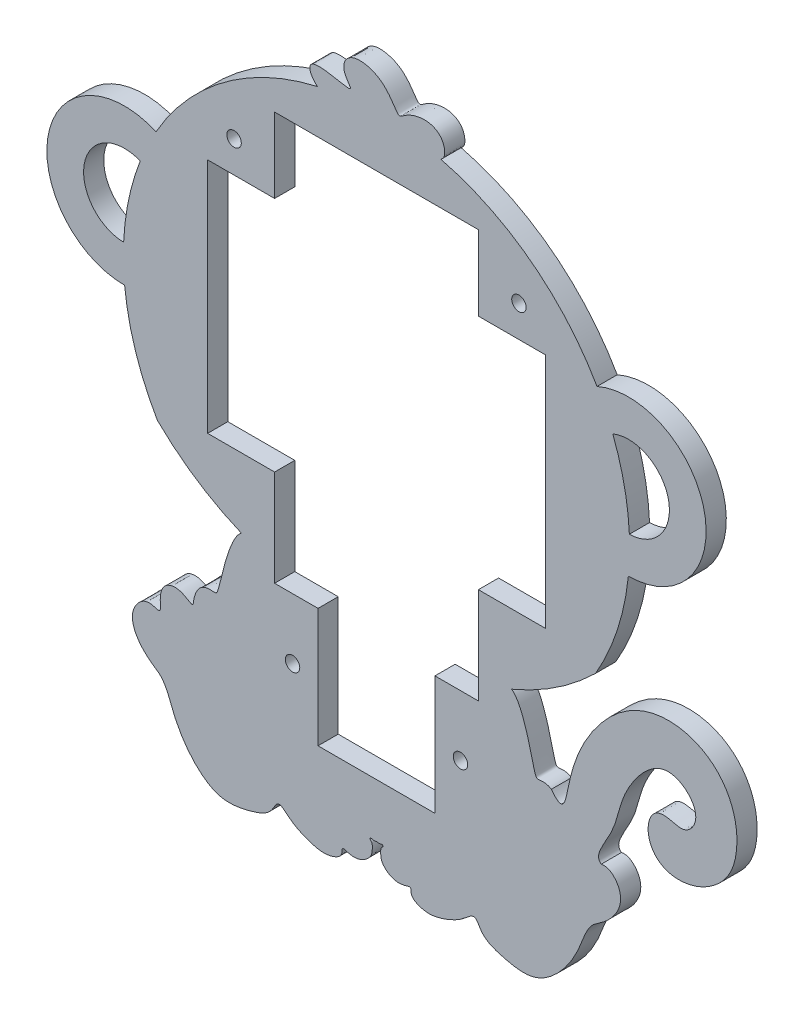
SolidWorks part; units mm, degrees
ref_plane "Front Plane" through (0, 0, 0) normal (0, 0, 1) x (1, 0, 0)
ref_plane "Top Plane" through (0, 0, 0) normal (0, 1, 0) x (1, 0, 0)
ref_plane "Right Plane" through (0, 0, 0) normal (1, 0, 0) x (0, 0, -1)
sketch "Model" plane through (0, 0, 0) normal (0, 0, 1) x (1, 0, 0)
  line L0 (-354.7776, 349.4226) -> (-354.7776, 392.0292) construction
  line L1 (-368.5276, 390.0292) -> (-368.5276, 362.0292)
  line L2 (-368.5276, 390.0292) -> (-341.0276, 390.0292)
  line L21 (-354.7776, 390.0292) -> (-354.7776, 362.0292)
  line L26 (-368.5276, 362.0292) -> (-341.0276, 362.0292)
  line L27 (-341.0276, 390.0292) -> (-341.0276, 362.0292)
  line L28 (-354.7776, 390.0292) -> (-354.7776, 497.7106) construction
  line L29 (-368.5276, 390.0292) -> (-378.7446, 390.0292)
  line L31 (-368.5276, 486.0185) -> (-378.7446, 486.0185)
  line L32 (-378.7446, 390.0292) -> (-378.7446, 486.0185)
  line L33 (-378.7446, 412.6938) -> (-394.4933, 412.6938)
  line L34 (-378.7446, 412.6938) -> (-378.7446, 468.4071)
  line L35 (-378.7446, 468.4071) -> (-394.4933, 468.4071)
  line L36 (-394.4933, 412.6938) -> (-394.4933, 468.4071)
  line L37 (-354.7776, 390.0292) -> (-368.5276, 390.0292)
  line L38 (-354.7776, 390.0292) -> (-354.7776, 486.0185)
  line L39 (-354.7776, 486.0185) -> (-368.5276, 486.0185)
  line L41 (-354.7776, 486.0185) -> (-341.0276, 486.0185)
  line L42 (-341.0276, 486.0185) -> (-330.8106, 486.0185)
  line L43 (-341.0276, 390.0292) -> (-330.8106, 390.0292)
  line L44 (-330.8106, 412.6938) -> (-315.0619, 412.6938)
  line L45 (-315.0619, 412.6938) -> (-315.0619, 468.4071)
  line L46 (-330.8106, 468.4071) -> (-315.0619, 468.4071)
  line L47 (-330.8106, 390.0292) -> (-330.8106, 486.0185)
  circle A0 centre (-295.506, 451.3512) radius 18.2563
  circle A1 centre (-295.506, 451.3512) radius 9.6191
  circle A2 centre (-414.0491, 451.3512) radius 9.6191
  circle A3 centre (-414.0491, 451.3512) radius 18.2562
  arc A4 (-354.7776, 392.0292) -> (-303.2483, 409.4214) centre (-346.9752, 453.9435) ccw
  arc A5 (-303.2483, 409.4214) -> (-354.7776, 497.7106) centre (-353.9365, 439.0196) ccw
  arc A6 (-354.7776, 497.7106) -> (-406.3069, 409.4214) centre (-355.6187, 439.0196) ccw
  arc A7 (-406.3069, 409.4214) -> (-354.7776, 392.0292) centre (-362.58, 453.9435) ccw
  circle A8 centre (-321.2776, 475.7792) radius 2.05 construction
  circle A9 centre (-388.2776, 475.7792) radius 2.05 construction
  circle A10 centre (-321.2776, 475.7792) radius 2.05 construction
  circle A11 centre (-388.2776, 475.7792) radius 2.05 construction
  circle A12 centre (-388.2776, 475.7792) radius 1.7
  circle A13 centre (-321.2776, 475.7792) radius 1.7
  circle A14 centre (-374.5276, 375.7792) radius 2.05 construction
  circle A15 centre (-335.0276, 375.7792) radius 2.05 construction
  circle A16 centre (-374.5276, 375.7792) radius 2.05 construction
  circle A17 centre (-335.0276, 375.7792) radius 2.05 construction
  circle A18 centre (-374.5276, 375.7792) radius 1.7
  circle A19 centre (-335.0276, 375.7792) radius 1.7
  spline S0 degree 5 poles (-386.5513, 396.3273) (-386.9161, 396.0792) (-387.366, 395.6344) (-387.8968, 394.8986) (-388.5033, 393.7572) (-389.1715, 392.131) (-389.5779, 391.0147) (-389.9703, 389.8193) (-390.4193, 388.3234) (-390.8333, 386.8049) (-391.2016, 385.3464) (-391.5167, 384.0353) (-391.7817, 382.9443) (-391.9754, 382.2094) (-392.154, 381.6648) (-392.3367, 381.3111) (-392.5515, 381.1299) (-392.8335, 381.0822) (-393.2115, 381.1155) (-393.6934, 381.1695) (-394.2612, 381.1826) (-394.881, 381.0994) (-395.5104, 380.8776) (-396.1059, 380.4945) (-396.6315, 379.9559) (-397.064, 379.2975) (-397.3921, 378.574) (-397.6173, 377.8496) (-397.7535, 377.1888) (-397.8274, 376.647) (-397.8791, 376.2603) (-397.9596, 376.0385) (-398.1148, 375.9725) (-398.366, 376.0408) (-398.7069, 376.2147) (-399.1201, 376.4601) (-399.5915, 376.7412) (-400.118, 377.0223) (-400.6998, 377.2689) (-401.4638, 377.484) (-402.3002, 377.5538) (-403.1741, 377.4267) (-404.0022, 377.0659) (-404.6982, 376.4644) (-405.1535, 375.8118) (-405.4613, 375.0322) (-405.6199, 374.1669) (-405.658, 373.2789) (-405.6265, 372.4425) (-405.5875, 371.7311) (-405.6037, 371.2053) (-405.7274, 370.9008) (-405.9901, 370.8167) (-406.3911, 370.9021) (-406.9056, 371.0748) (-407.4962, 371.2433) (-408.1222, 371.3275) (-408.7511, 371.2827) (-409.3596, 371.0975) (-409.9312, 370.7828) (-410.4544, 370.3635) (-410.9212, 369.8697) (-411.3251, 369.3269) (-411.6596, 368.7503) (-411.9191, 368.1478) (-412.0987, 367.5224) (-412.1944, 366.8744) (-412.2033, 366.204) (-412.0922, 365.2374) (-411.7958, 364.2405) (-411.2536, 363.0979) (-410.5055, 362.004) (-409.6286, 361.0209) (-408.9407, 360.363) (-408.2617, 359.7955) (-407.7193, 359.3836) (-407.2138, 359.0282) (-406.7532, 358.7179) (-406.3372, 358.4326) (-405.9584, 358.1461) (-405.6064, 357.8322) (-405.2709, 357.469) (-404.9452, 357.0452) (-404.6288, 356.5637) (-404.3252, 356.0366) (-404.0394, 355.4808) (-403.7755, 354.9137) (-403.4863, 354.2349) (-403.2244, 353.5638) (-402.972, 352.8931) (-402.7045, 352.203) (-402.4017, 351.478) (-402.0626, 350.7211) (-401.6746, 349.928) (-401.239, 349.111) (-400.7631, 348.2898) (-400.2543, 347.482) (-399.7226, 346.693) (-399.1634, 345.9321) (-398.5743, 345.1992) (-397.9495, 344.4888) (-397.2819, 343.7971) (-396.6937, 343.2329) (-395.9467, 342.5739) (-395.1459, 341.9478) (-394.2909, 341.3752) (-393.3842, 340.8821) (-392.43, 340.4917) (-391.606, 340.244) (-390.756, 340.0794) (-389.8831, 339.9983) (-388.9906, 339.995) (-388.0822, 340.0607) (-387.1626, 340.184) (-386.2377, 340.3533) (-385.315, 340.5579) (-384.404, 340.7898) (-383.5163, 341.0454) (-382.6665, 341.327) (-381.8713, 341.6429) (-381.1468, 342.0028) (-380.5061, 342.4143) (-379.9577, 342.8796) (-379.5022, 343.3918) (-379.1308, 343.9312) (-378.8219, 344.461) (-378.5447, 344.9321) (-378.2678, 345.2959) (-377.9655, 345.5144) (-377.6259, 345.571) (-377.2571, 345.4813) (-376.8758, 345.2788) (-376.4963, 345.0025) (-376.1171, 344.6823) (-375.7208, 344.3352) (-375.2832, 343.9706) (-374.7791, 343.5936) (-374.1903, 343.2075) (-373.3777, 342.7411) (-372.4498, 342.2849) (-371.4489, 341.8618) (-370.4344, 341.4969) (-369.4571, 341.2116) (-368.6859, 341.0352) (-367.9644, 340.9249) (-367.2855, 340.8811) (-366.6359, 340.9021) (-366.0015, 340.9842) (-365.3739, 341.1239) (-364.7563, 341.3185) (-364.1709, 341.5681) (-363.6579, 341.8743) (-363.2584, 342.2351) (-362.9996, 342.6398) (-362.8828, 343.0653) (-362.8624, 343.4679) (-362.8603, 343.7943) (-362.8008, 344.002) (-362.6453, 344.0822) (-362.4039, 344.0645) (-362.091, 343.9838) (-361.7122, 343.8689) (-361.2711, 343.747) (-360.7722, 343.6434) (-360.2251, 343.5846) (-359.6439, 343.594) (-359.0456, 343.6889) (-358.3311, 343.9146) (-357.653, 344.2718) (-357.0557, 344.716) (-356.5775, 345.1787) (-356.2334, 345.621) (-356.0331, 345.9754) (-355.9027, 346.3429) (-355.8208, 346.7573) (-355.7698, 347.2366) (-355.7451, 347.7596) (-355.7624, 348.2488) (-355.8386, 348.6234) (-355.9777, 348.8376) (-356.1508, 348.9418) (-356.2927, 349.0757) (-356.3365, 349.2881) (-356.2363, 349.4431) (-355.9971, 349.4554) (-355.6775, 349.3823) (-355.3456, 349.3188) (-355.1001, 349.3199) (-354.9324, 349.357) (-354.828, 349.398) (-354.7776, 349.4226) knots 0 0 0 0 0 0 0.02 0.025 0.03 0.035 0.04 0.045 0.05 0.06 0.065 0.07 0.075 0.08 0.085 0.09 0.095 0.1 0.105 0.11 0.115 0.12 0.125 0.13 0.135 0.14 0.145 0.15 0.155 0.16 0.165 0.17 0.175 0.18 0.185 0.19 0.195 0.2 0.205 0.21 0.22 0.225 0.23 0.235 0.24 0.245 0.25 0.255 0.26 0.265 0.27 0.275 0.28 0.285 0.29 0.295 0.3 0.305 0.31 0.315 0.32 0.325 0.33 0.335 0.34 0.345 0.35 0.355 0.36 0.375 0.38 0.39 0.395 0.4 0.405 0.41 0.415 0.42 0.425 0.43 0.435 0.44 0.445 0.45 0.455 0.46 0.465 0.47 0.48 0.485 0.49 0.495 0.5 0.51 0.515 0.52 0.525 0.53 0.54 0.545 0.55 0.555 0.56 0.565 0.575 0.58 0.585 0.59 0.595 0.6 0.605 0.61 0.615 0.62 0.625 0.63 0.635 0.64 0.645 0.65 0.655 0.66 0.665 0.67 0.675 0.68 0.685 0.69 0.695 0.7 0.705 0.71 0.715 0.72 0.725 0.73 0.735 0.74 0.745 0.755 0.76 0.765 0.77 0.775 0.78 0.785 0.79 0.795 0.8 0.805 0.81 0.815 0.82 0.825 0.83 0.835 0.84 0.845 0.85 0.855 0.86 0.865 0.87 0.875 0.88 0.885 0.89 0.895 0.905 0.91 0.915 0.92 0.925 0.93 0.935 0.94 0.945 0.95 0.955 0.96 0.965 0.97 0.975 0.98 0.985 0.99 0.995 1 1 1 1 1 1 weights 1 1 1 1 1 1 1 1 1 1 1 1 1 1 1 1 1 1 1 1 1 1 1 1 1 1 1 1 1 1 1 1 1 1 1 1 1 1 1 1 1 1 1 1 1 1 1 1 1 1 1 1 1 1 1 1 1 1 1 1 1 1 1 1 1 1 1 1 1 1 1 1 1 1 1 1 1 1 1 1 1 1 1 1 1 1 1 1 1 1 1 1 1 1 1 1 1 1 1 1 1 1 1 1 1 1 1 1 1 1 1 1 1 1 1 1 1 1 1 1 1 1 1 1 1 1 1 1 1 1 1 1 1 1 1 1 1 1 1 1 1 1 1 1 1 1 1 1 1 1 1 1 1 1 1 1 1 1 1 1 1 1 1 1 1 1 1 1 1 1 1 1 1 1 1 1 1 1 1 1 1 1 1 1 1 1 1 1 1 1 1
  spline S1 degree 5 poles (-323.0039, 396.3273) (-322.6391, 396.0792) (-322.1892, 395.6344) (-321.6584, 394.8986) (-321.0519, 393.7572) (-320.3837, 392.131) (-319.9773, 391.0147) (-319.5849, 389.8193) (-319.1359, 388.3234) (-318.7219, 386.8049) (-318.3536, 385.3464) (-318.0385, 384.0353) (-317.7735, 382.9443) (-317.5798, 382.2094) (-317.4012, 381.6648) (-317.2185, 381.3111) (-317.0037, 381.1299) (-316.7217, 381.0822) (-316.3437, 381.1155) (-315.8618, 381.1695) (-315.294, 381.1826) (-314.6741, 381.0994) (-314.0448, 380.8776) (-313.4493, 380.4945) (-312.9237, 379.9559) (-312.4912, 379.2975) (-312.1631, 378.574) (-311.9379, 377.8496) (-311.8017, 377.1888) (-311.7278, 376.647) (-311.6761, 376.2603) (-311.5956, 376.0385) (-311.4404, 375.9725) (-311.1892, 376.0408) (-310.8483, 376.2147) (-310.4351, 376.4601) (-309.9637, 376.7412) (-309.4372, 377.0223) (-308.8554, 377.2689) (-308.0914, 377.484) (-307.2549, 377.5538) (-306.3811, 377.4267) (-305.553, 377.0659) (-304.857, 376.4644) (-304.4017, 375.8118) (-304.0939, 375.0322) (-303.9353, 374.1669) (-303.8972, 373.2789) (-303.9287, 372.4425) (-303.9677, 371.7311) (-303.9515, 371.2053) (-303.8278, 370.9008) (-303.5651, 370.8167) (-303.1641, 370.9021) (-302.6496, 371.0748) (-302.0589, 371.2433) (-301.433, 371.3275) (-300.8041, 371.2827) (-300.1956, 371.0975) (-299.624, 370.7828) (-299.1008, 370.3635) (-298.634, 369.8697) (-298.2301, 369.3269) (-297.8956, 368.7503) (-297.6361, 368.1478) (-297.4565, 367.5224) (-297.3608, 366.8744) (-297.3519, 366.204) (-297.463, 365.2374) (-297.7594, 364.2405) (-298.3016, 363.0979) (-299.0496, 362.004) (-299.9266, 361.0209) (-300.6145, 360.363) (-301.2935, 359.7955) (-301.8359, 359.3836) (-302.3414, 359.0282) (-302.8019, 358.7179) (-303.218, 358.4326) (-303.5968, 358.1461) (-303.9488, 357.8322) (-304.2843, 357.469) (-304.61, 357.0452) (-304.9264, 356.5637) (-305.23, 356.0366) (-305.5158, 355.4808) (-305.7797, 354.9137) (-306.0689, 354.2349) (-306.3308, 353.5638) (-306.5832, 352.8931) (-306.8507, 352.203) (-307.1535, 351.478) (-307.4926, 350.7211) (-307.8805, 349.928) (-308.3162, 349.111) (-308.7921, 348.2898) (-309.3008, 347.482) (-309.8326, 346.693) (-310.3918, 345.9321) (-310.9809, 345.1992) (-311.6057, 344.4888) (-312.2733, 343.7971) (-312.8615, 343.2329) (-313.6085, 342.5739) (-314.4093, 341.9478) (-315.2643, 341.3752) (-316.171, 340.8821) (-317.1251, 340.4917) (-317.9492, 340.244) (-318.7992, 340.0794) (-319.6721, 339.9983) (-320.5646, 339.995) (-321.473, 340.0607) (-322.3926, 340.184) (-323.3175, 340.3533) (-324.2402, 340.5579) (-325.1512, 340.7898) (-326.0389, 341.0454) (-326.8887, 341.327) (-327.6839, 341.6429) (-328.4084, 342.0028) (-329.049, 342.4143) (-329.5975, 342.8796) (-330.053, 343.3918) (-330.4244, 343.9312) (-330.7333, 344.461) (-331.0105, 344.9321) (-331.2874, 345.2959) (-331.5897, 345.5144) (-331.9293, 345.571) (-332.298, 345.4813) (-332.6794, 345.2788) (-333.0589, 345.0025) (-333.4381, 344.6823) (-333.8343, 344.3352) (-334.272, 343.9706) (-334.7761, 343.5936) (-335.3649, 343.2075) (-336.1775, 342.7411) (-337.1053, 342.2849) (-338.1063, 341.8618) (-339.1207, 341.4969) (-340.0981, 341.2116) (-340.8693, 341.0352) (-341.5908, 340.9249) (-342.2697, 340.8811) (-342.9193, 340.9021) (-343.5537, 340.9842) (-344.1813, 341.1239) (-344.7989, 341.3185) (-345.3842, 341.5681) (-345.8972, 341.8743) (-346.2968, 342.2351) (-346.5556, 342.6398) (-346.6724, 343.0653) (-346.6928, 343.4679) (-346.6949, 343.7943) (-346.7544, 344.002) (-346.9099, 344.0822) (-347.1513, 344.0645) (-347.4642, 343.9838) (-347.843, 343.8689) (-348.2841, 343.747) (-348.783, 343.6434) (-349.33, 343.5846) (-349.9113, 343.594) (-350.5096, 343.6889) (-351.2241, 343.9146) (-351.9022, 344.2718) (-352.4995, 344.716) (-352.9777, 345.1787) (-353.3218, 345.621) (-353.5221, 345.9754) (-353.6525, 346.3429) (-353.7344, 346.7573) (-353.7854, 347.2366) (-353.8101, 347.7596) (-353.7928, 348.2488) (-353.7166, 348.6234) (-353.5775, 348.8376) (-353.4043, 348.9418) (-353.2625, 349.0757) (-353.2187, 349.2881) (-353.3188, 349.4431) (-353.5581, 349.4554) (-353.8776, 349.3823) (-354.2096, 349.3188) (-354.4551, 349.3199) (-354.6228, 349.357) (-354.7272, 349.398) (-354.7776, 349.4226) knots 0 0 0 0 0 0 0.02 0.025 0.03 0.035 0.04 0.045 0.05 0.06 0.065 0.07 0.075 0.08 0.085 0.09 0.095 0.1 0.105 0.11 0.115 0.12 0.125 0.13 0.135 0.14 0.145 0.15 0.155 0.16 0.165 0.17 0.175 0.18 0.185 0.19 0.195 0.2 0.205 0.21 0.22 0.225 0.23 0.235 0.24 0.245 0.25 0.255 0.26 0.265 0.27 0.275 0.28 0.285 0.29 0.295 0.3 0.305 0.31 0.315 0.32 0.325 0.33 0.335 0.34 0.345 0.35 0.355 0.36 0.375 0.38 0.39 0.395 0.4 0.405 0.41 0.415 0.42 0.425 0.43 0.435 0.44 0.445 0.45 0.455 0.46 0.465 0.47 0.48 0.485 0.49 0.495 0.5 0.51 0.515 0.52 0.525 0.53 0.54 0.545 0.55 0.555 0.56 0.565 0.575 0.58 0.585 0.59 0.595 0.6 0.605 0.61 0.615 0.62 0.625 0.63 0.635 0.64 0.645 0.65 0.655 0.66 0.665 0.67 0.675 0.68 0.685 0.69 0.695 0.7 0.705 0.71 0.715 0.72 0.725 0.73 0.735 0.74 0.745 0.755 0.76 0.765 0.77 0.775 0.78 0.785 0.79 0.795 0.8 0.805 0.81 0.815 0.82 0.825 0.83 0.835 0.84 0.845 0.85 0.855 0.86 0.865 0.87 0.875 0.88 0.885 0.89 0.895 0.905 0.91 0.915 0.92 0.925 0.93 0.935 0.94 0.945 0.95 0.955 0.96 0.965 0.97 0.975 0.98 0.985 0.99 0.995 1 1 1 1 1 1 weights 1 1 1 1 1 1 1 1 1 1 1 1 1 1 1 1 1 1 1 1 1 1 1 1 1 1 1 1 1 1 1 1 1 1 1 1 1 1 1 1 1 1 1 1 1 1 1 1 1 1 1 1 1 1 1 1 1 1 1 1 1 1 1 1 1 1 1 1 1 1 1 1 1 1 1 1 1 1 1 1 1 1 1 1 1 1 1 1 1 1 1 1 1 1 1 1 1 1 1 1 1 1 1 1 1 1 1 1 1 1 1 1 1 1 1 1 1 1 1 1 1 1 1 1 1 1 1 1 1 1 1 1 1 1 1 1 1 1 1 1 1 1 1 1 1 1 1 1 1 1 1 1 1 1 1 1 1 1 1 1 1 1 1 1 1 1 1 1 1 1 1 1 1 1 1 1 1 1 1 1 1 1 1 1 1 1 1 1 1 1 1
  spline S2 degree 5 poles (-313.6608, 380.6036) (-313.4447, 380.3201) (-313.0302, 379.8091) (-312.4617, 379.2104) (-311.8099, 378.7481) (-311.1658, 378.7209) (-310.6734, 379.2168) (-310.2927, 380.1782) (-309.9686, 381.5239) (-309.6406, 383.1622) (-309.2509, 385.0015) (-308.7553, 386.9633) (-308.0017, 389.3938) (-307.0301, 391.8531) (-305.8363, 394.2764) (-304.438, 396.6235) (-302.856, 398.8596) (-301.4232, 400.6299) (-299.5708, 402.6142) (-297.5538, 404.3848) (-295.3743, 405.8881) (-292.6508, 407.2693) (-289.33, 408.2696) (-286.299, 408.5941) (-283.2651, 408.3445) (-280.3791, 407.5391) (-278.0928, 406.4785) (-276.3489, 405.3668) (-274.4851, 403.7878) (-272.9371, 401.946) (-271.7278, 399.9069) (-270.8571, 397.7451) (-270.3065, 395.5388) (-270.0462, 393.71) (-269.965, 391.9301) (-270.041, 390.2346) (-270.2523, 388.6524) (-270.5799, 387.2019) (-271.0097, 385.8888) (-271.5359, 384.701) (-272.1612, 383.6109) (-272.8958, 382.5869) (-273.7555, 381.6014) (-274.7609, 380.6417) (-275.9355, 379.7174) (-277.2973, 378.8569) (-278.8515, 378.1044) (-280.5823, 377.5164) (-282.4459, 377.1586) (-284.3607, 377.1036) (-286.2191, 377.417) (-287.9032, 378.1427) (-289.299, 379.2867) (-290.311, 380.8037) (-290.8776, 382.5789) (-290.9832, 384.4209) (-290.6506, 386.112) (-289.936, 387.4514) (-288.9223, 388.2997) (-287.7148, 388.6275) (-286.4328, 388.5495) (-285.1876, 388.2576) (-284.0619, 387.9667) (-283.0865, 387.8525) (-282.2242, 388) (-281.4248, 388.4326) (-280.673, 389.1343) (-280.0427, 390.0762) (-279.6515, 391.2145) (-279.6146, 392.4895) (-279.9934, 393.8227) (-280.764, 395.118) (-281.8511, 396.2738) (-283.152, 397.1938) (-284.5629, 397.798) (-286.0086, 398.0348) (-287.4505, 397.8849) (-288.8706, 397.3556) (-290.2614, 396.4772) (-291.6143, 395.2987) (-292.9061, 393.8845) (-294.101, 392.3076) (-295.162, 390.6429) (-296.0582, 388.9596) (-296.775, 387.314) (-297.3214, 385.7431) (-297.7428, 384.2552) (-298.1147, 382.8324) (-298.5188, 381.4451) (-299.0233, 380.0639) (-299.6638, 378.6704) (-300.4174, 377.2729) (-301.2032, 375.907) (-301.9108, 374.6227) (-302.4229, 373.4731) (-302.6383, 372.5046) (-302.5279, 371.8953) (-302.2784, 371.535) (-302.0378, 371.3378) (-301.8989, 371.25) knots 0 0 0 0 0 0 0.01 0.02 0.03 0.04 0.05 0.06 0.07 0.08 0.09 0.1 0.11 0.13 0.14 0.15 0.16 0.17 0.18 0.2 0.21 0.22 0.24 0.26 0.27 0.28 0.29 0.3 0.31 0.33 0.34 0.35 0.36 0.37 0.38 0.39 0.4 0.41 0.42 0.43 0.44 0.45 0.46 0.47 0.48 0.49 0.5 0.51 0.52 0.53 0.54 0.55 0.56 0.57 0.58 0.59 0.6 0.61 0.62 0.63 0.64 0.65 0.66 0.67 0.68 0.69 0.7 0.71 0.72 0.73 0.74 0.75 0.76 0.77 0.78 0.79 0.8 0.81 0.82 0.83 0.84 0.85 0.86 0.87 0.88 0.89 0.9 0.91 0.92 0.93 0.94 0.95 0.96 0.97 0.98 0.99 1 1 1 1 1 1 weights 1 1 1 1 1 1 1 1 1 1 1 1 1 1 1 1 1 1 1 1 1 1 1 1 1 1 1 1 1 1 1 1 1 1 1 1 1 1 1 1 1 1 1 1 1 1 1 1 1 1 1 1 1 1 1 1 1 1 1 1 1 1 1 1 1 1 1 1 1 1 1 1 1 1 1 1 1 1 1 1 1 1 1 1 1 1 1 1 1 1 1 1 1 1 1 1 1 1 1 1
  spline S3 degree 5 poles (-368.6485, 496.2522) (-368.7445, 496.3189) (-368.9332, 496.4614) (-369.2068, 496.7025) (-369.5526, 497.079) (-369.9454, 497.6352) (-370.274, 498.2589) (-370.4903, 498.915) (-370.5107, 499.5416) (-370.2384, 500.0643) (-369.5991, 500.4175) (-368.5716, 500.5624) (-367.2236, 500.5088) (-365.6871, 500.3043) (-364.1304, 500.0214) (-362.7304, 499.745) (-361.6458, 499.5606) (-360.9878, 499.5411) (-360.7964, 499.7361) (-361.0037, 500.1558) (-361.4562, 500.7754) (-361.9696, 501.5464) (-362.3683, 502.407) (-362.5408, 503.2925) (-362.4544, 504.1433) (-362.127, 504.907) (-361.609, 505.5429) (-360.9624, 506.0248) (-360.2377, 506.3463) (-359.4651, 506.519) (-358.6621, 506.5638) (-357.8368, 506.5034) (-356.9934, 506.3554) (-356.1367, 506.1232) (-355.2752, 505.7947) (-354.4199, 505.3529) (-353.5839, 504.7839) (-352.7824, 504.0858) (-352.0321, 503.2767) (-351.3511, 502.4053) (-350.7568, 501.5504) (-350.2591, 500.8009) (-349.8549, 500.2405) (-349.5224, 499.9306) (-349.215, 499.8941) (-348.8555, 500.0985) (-348.3621, 500.4755) (-347.6717, 500.9383) (-346.77, 501.4022) (-345.6888, 501.7923) (-344.4899, 502.0451) (-343.2539, 502.1125) (-342.0666, 501.9648) (-341.0067, 501.594) (-340.1326, 501.0174) (-339.4704, 500.2805) (-339.0219, 499.4471) (-338.7725, 498.5899) (-338.6988, 497.7804) (-338.776, 497.0807) (-338.9866, 496.5313) (-339.2553, 496.2274) (-339.5119, 496.0787) (-339.7073, 496.0148) (-339.8111, 495.9917) knots 0 0 0 0 0 0 0.016667 0.033333 0.05 0.066667 0.083333 0.1 0.116667 0.133333 0.15 0.166667 0.183333 0.2 0.216667 0.233333 0.25 0.266667 0.283333 0.3 0.316667 0.333333 0.35 0.366667 0.383333 0.4 0.416667 0.433333 0.45 0.466667 0.483333 0.5 0.516667 0.533333 0.55 0.566667 0.583333 0.6 0.616667 0.633333 0.65 0.666667 0.683333 0.7 0.716667 0.733333 0.75 0.766667 0.783333 0.8 0.816667 0.833333 0.85 0.866667 0.883333 0.9 0.916667 0.933333 0.95 0.966667 0.983333 1 1 1 1 1 1 weights 1 1 1 1 1 1 1 1 1 1 1 1 1 1 1 1 1 1 1 1 1 1 1 1 1 1 1 1 1 1 1 1 1 1 1 1 1 1 1 1 1 1 1 1 1 1 1 1 1 1 1 1 1 1 1 1 1 1 1 1 1 1 1 1 1
  dimension "D4" = 3.4
  dimension "D5" = 3.4
  dimension "D6" = 3.4
  dimension "D2" = 13.75
  dimension "D3" = 2
  dimension "D1" = 28
extrude "Boss-Extrude1" add sketch "Model" along normal blind 4.75 contours A6 A7 A4 A5 A0 A3 | A3 A6 A2 | A2 A6 | A6 A3 A2 | A1 A5 A0 | A1 A5 | A5 A1 A0 | S2 S1 A4 L47 L43 L27 L26 L1 L29 L32 A7 S0 | S2 S1 | S3 A6 A5 region at (-369.8065, 376.0292, 0) region at (-382.1837, 396.3619, 0) region at (-404.0204, 449.2347, 0) region at (-431.4752, 455.029, 0) region at (-305.971, 377.819, 0) region at (-294.8154, 437.3981, 0) region at (-305.5348, 449.2347, 0) region at (-409.3752, 450.3648, 0) region at (-300.18, 450.3648, 0) region at (-354.5371, 500.3437, 0)
